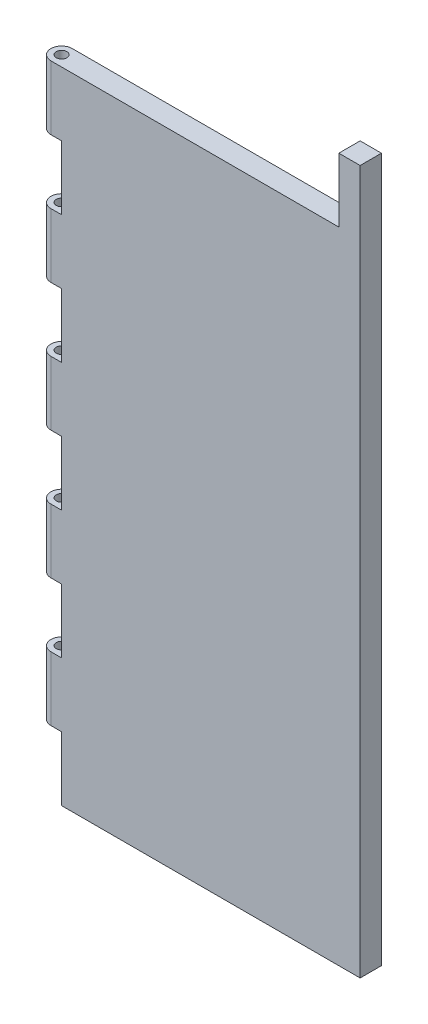
SolidWorks part; units mm, degrees
ref_plane "Front Plane" through (0, 0, 0) normal (0, 0, 1) x (1, 0, 0)
ref_plane "Top Plane" through (0, 0, 0) normal (0, 1, 0) x (1, 0, 0)
ref_plane "Right Plane" through (0, 0, 0) normal (1, 0, 0) x (0, 0, -1)
sketch "Sketch1" plane through (0, 0, 0) normal (0, 0, 1) x (1, 0, 0)
  line L1 (0, 0) -> (150, 0)
  line L2 (0, 0) -> (0, 300)
  line L3 (0, 300) -> (140, 300)
  line L4 (150, 0) -> (150, 206.3087)
  line L6 (150, 206.3087) -> (150, 330)
  line L7 (150, 330) -> (140, 330)
  line L8 (140, 300) -> (140, 330)
  dimension "D1" = 150
  dimension "D2" = 300
  dimension "D3" = 10
  dimension "D4" = 30
  dimension "D5" = 123.6913
extrude "Boss-Extrude1" add sketch "Sketch1" along normal blind 10
sketch "Sketch2" plane through (0, 0, 10) normal (0, 0, 1) x (1, 0, 0)
  line L0 (0, 60) -> (10, 60)
  line L1 (0, 0) -> (10, 0)
  line L2 (0, 0) -> (0, 30)
  line L3 (0, 30) -> (10, 30)
  line L4 (10, 0) -> (10, 30)
  line L5 (0, 60) -> (0, 90)
  line L6 (0, 90) -> (10, 90)
  line L7 (10, 60) -> (10, 90)
  line L8 (0, 120) -> (10, 120)
  line L9 (0, 120) -> (0, 150)
  line L10 (0, 150) -> (10, 150)
  line L11 (10, 120) -> (10, 150)
  line L12 (0, 180) -> (10, 180)
  line L13 (0, 180) -> (0, 210)
  line L14 (0, 210) -> (10, 210)
  line L15 (10, 180) -> (10, 210)
  line L16 (0, 240) -> (10, 240)
  line L17 (0, 240) -> (0, 270)
  line L18 (0, 270) -> (10, 270)
  line L19 (10, 240) -> (10, 270)
  dimension "D1" = 30
  dimension "D2" = 10
  dimension "D4" = 30
  dimension "D3" = 5
extrude "Cut-Extrude1" cut sketch "Sketch2" against normal through all
sketch "Sketch3" plane through (0, 300, 0) normal (0, 1, 0) x (1, 0, 0)
  line L1 (140, -10) -> (0, -10) construction
  line L2 (0, -10) -> (0, 0) construction
  circle A0 centre (5, -5) radius 2.5
  dimension "D1" = 5
  dimension "D2" = 5
  dimension "D3" = 5
extrude "Cut-Extrude2" cut sketch "Sketch3" against normal through all contours A0
fillet "Fillet3" 2 edges at (0, 285, 10) (0, 285, 0) type full round first side face at (28.3333, 165, 10) second side face at (28.3333, 165, 0) middle face at (0, 285, 5)
fillet "Fillet4" 2 edges at (0, 225, 10) (0, 225, 0) type full round first side face at (28.75, 165, 10) second side face at (28.75, 165, 0) middle face at (0, 225, 5)
fillet "Fillet5" 2 edges at (0, 165, 10) (0, 165, 0) type full round first side face at (29.1667, 165, 10) second side face at (29.1667, 165, 0) middle face at (0, 165, 5)
fillet "Fillet6" 2 edges at (0, 105, 10) (0, 105, 0) type full round first side face at (29.5833, 165, 10) second side face at (29.5833, 165, 0) middle face at (0, 105, 5)
fillet "Fillet7" 2 edges at (0, 45, 10) (0, 45, 0) type full round first side face at (30, 165, 10) second side face at (30, 165, 0) middle face at (0, 45, 5)
